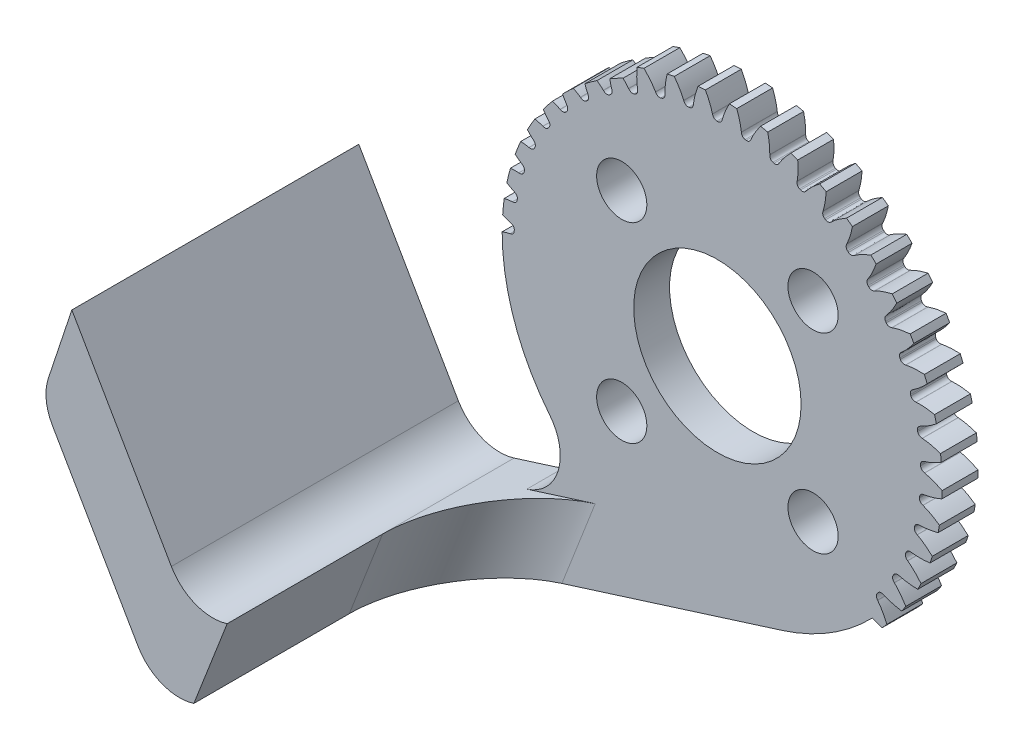
SolidWorks part; units mm, degrees
note: The reader was unsure of these and kept them because the rebuilt part matched: shared geometry of "Sketch1<12>".
ref_plane "Front Plane" through (0, 0, 0) normal (0, 0, 1) x (1, 0, 0)
ref_plane "Top Plane" through (0, 0, 0) normal (0, 1, 0) x (1, 0, 0)
ref_plane "Right Plane" through (0, 0, 0) normal (1, 0, 0) x (0, 0, -1)
sketch "Sketch1" plane through (0, 0, 0) normal (0, 0, 1) x (-1, 0, 0)
  line L0 (-997.4582, 1.777) -> (0.6857, 1.777) construction
  line L3 (27.2085, 36.8505) -> (35.5323, 22.4334)
  line L11 (35.5323, 22.4334) -> (37.4944, 28.3526)
  line L14 (25.33, 45.8357) -> (-2.8709, 36.9439)
  line L15 (22.5416, 38.6653) -> (18.4787, 37.3843)
  line L17 (29.9969, 44.0208) -> (37.1617, 31.6112)
  line L18 (22.5416, 38.6653) -> (25.33, 45.8357)
  line L20 (-14.6013, 17.1719) -> (-14.584, 17.1703)
  line L21 (10.5418, 11.777) -> (-5.4582, 11.777) construction
  line L22 (10.5418, 11.777) -> (10.5418, 27.777) construction
  line L23 (10.5418, 27.777) -> (-5.4582, 27.777) construction
  line L24 (-5.4582, 11.777) -> (-5.4582, 27.777) construction
  line L25 (2.5418, 27.777) -> (2.5418, 11.777) construction
  line L26 (10.5418, 19.777) -> (-5.4582, 19.777) construction
  line L27 (-14.4428, 16.3692) -> (-14.4584, 16.3618)
  line L28 (-14.0719, 14.8114) -> (-14.0546, 14.8122)
  line L29 (-13.8032, 14.0386) -> (-13.8177, 14.0291)
  line L30 (-13.2191, 12.5475) -> (-13.2021, 12.5507)
  line L31 (-12.8455, 11.8196) -> (-12.8585, 11.8082)
  line L32 (-12.0596, 10.4244) -> (-12.0432, 10.4299)
  line L33 (-11.5883, 9.7556) -> (-11.5996, 9.7425)
  line L34 (-10.6158, 8.4833) -> (-10.6003, 8.491)
  line L35 (-10.0561, 7.8866) -> (-10.0654, 7.872)
  line L36 (-8.916, 6.762) -> (-8.9017, 6.7718)
  line L37 (-8.2786, 6.249) -> (-8.2859, 6.2333)
  line L38 (-6.9931, 5.2941) -> (-6.9804, 5.3058)
  line L39 (-6.2906, 4.8747) -> (-6.2956, 4.8582)
  line L40 (-4.8847, 4.108) -> (-4.8737, 4.1214)
  line L41 (-4.1307, 3.7905) -> (-4.1333, 3.7734)
  line L42 (-2.6317, 3.2269) -> (-2.6227, 3.2417)
  line L43 (-1.8408, 3.0175) -> (-1.841, 3.0002)
  line L44 (-0.278, 2.668) -> (-0.2712, 2.6838)
  line L45 (0.5343, 2.5706) -> (0.5365, 2.5535)
  line L46 (2.1305, 2.442) -> (2.1351, 2.4587)
  line L47 (2.9485, 2.4587) -> (2.9531, 2.442)
  line L48 (4.5471, 2.5535) -> (4.5493, 2.5706)
  line L49 (5.3548, 2.6838) -> (5.3617, 2.668)
  line L50 (6.9246, 3.0002) -> (6.9244, 3.0175)
  line L51 (7.7063, 3.2417) -> (7.7153, 3.2269)
  line L52 (9.2169, 3.7734) -> (9.2143, 3.7905)
  line L53 (9.9573, 4.1214) -> (9.9683, 4.108)
  line L54 (11.3792, 4.8582) -> (11.3742, 4.8747)
  line L55 (12.064, 5.3058) -> (12.0767, 5.2941)
  line L56 (13.3695, 6.2333) -> (13.3623, 6.249)
  line L57 (13.9854, 6.7718) -> (13.9996, 6.762)
  line L58 (15.149, 7.872) -> (15.1397, 7.8866)
  line L59 (15.684, 8.491) -> (15.6994, 8.4833)
  line L60 (16.6832, 9.7425) -> (16.6719, 9.7556)
  line L61 (17.1268, 10.4299) -> (17.1432, 10.4244)
  line L62 (17.9421, 11.8082) -> (17.9291, 11.8196)
  line L63 (18.2857, 12.5507) -> (18.3027, 12.5475)
  line L64 (18.9013, 14.0291) -> (18.8868, 14.0386)
  line L65 (19.1382, 14.8122) -> (19.1555, 14.8114)
  line L66 (19.542, 16.3618) -> (19.5264, 16.3692)
  line L67 (19.6676, 17.1703) -> (19.6849, 17.1719)
  line L68 (19.8519, 18.761) -> (19.8354, 18.7662)
  line L69 (19.8638, 19.5791) -> (19.8806, 19.5831)
  line L104 (-10.8652, 30.7736) -> (-10.8548, 30.7597)
  line L105 (-11.3556, 30.1188) -> (-11.3716, 30.1254)
  line L106 (-12.2651, 28.8007) -> (-12.253, 28.7884)
  line L107 (-12.6596, 28.084) -> (-12.6764, 28.0884)
  line L108 (-13.3769, 26.6522) -> (-13.3631, 26.6417)
  line L109 (-13.6678, 25.8875) -> (-13.685, 25.8895)
  line L110 (-14.1788, 24.3698) -> (-14.1637, 24.3613)
  line L111 (-14.3605, 23.5721) -> (-14.3778, 23.5717)
  line L112 (-14.6552, 21.9981) -> (-14.6391, 21.9918)
  line L113 (-14.7242, 21.1828) -> (-14.7412, 21.18)
  line L114 (-14.797, 19.5831) -> (-14.7802, 19.5791)
  line L115 (-14.7518, 18.7662) -> (-14.7683, 18.761)
  arc A0 (-2.8709, 36.9439) -> (-10.4063, 32.2809) centre (2.5418, 19.777) ccw
  circle A2 centre (2.5418, 19.777) radius 7
  circle A4 centre (-5.4582, 27.777) radius 2.1
  circle A5 centre (10.5418, 27.777) radius 2.1
  circle A6 centre (10.5418, 11.777) radius 2.1
  circle A7 centre (-5.4582, 11.777) radius 2.1
  arc A12 (29.9969, 44.0208) -> (25.33, 45.8357) centre (26.5328, 42.0208) ccw
  arc A13 (37.4944, 28.3526) -> (37.1617, 31.6112) centre (33.6976, 29.6112) ccw
  arc A18 (18.4787, 37.3843) -> (16.5652, 31.0617) centre (19.6815, 33.5694) ccw
  arc A19 (27.2085, 36.8505) -> (22.5416, 38.6653) centre (23.7444, 34.8505) ccw
  arc A20 (-16.1848, 18.118) -> (-16.1206, 17.5063) centre (2.5418, 19.777) ccw
  arc A21 (-14.2083, 16.8729) -> (-14.1914, 16.7771) centre (2.5418, 19.777) ccw
  arc A22 (-15.7717, 15.5279) -> (-15.6229, 14.9311) centre (2.5418, 19.777) ccw
  arc A23 (-13.6411, 14.57) -> (-13.6111, 14.4775) centre (2.5418, 19.777) ccw
  arc A24 (-15.0021, 13.0205) -> (-14.7717, 12.4503) centre (2.5418, 19.777) ccw
  arc A25 (-12.7589, 12.3685) -> (-12.7163, 12.281) centre (2.5418, 19.777) ccw
  arc A26 (-13.891, 10.6446) -> (-13.5835, 10.112) centre (2.5418, 19.777) ccw
  arc A27 (-11.579, 10.3111) -> (-11.5246, 10.2305) centre (2.5418, 19.777) ccw
  arc A28 (-12.4601, 8.4465) -> (-12.0815, 7.9618) centre (2.5418, 19.777) ccw
  arc A29 (-10.1241, 8.438) -> (-10.0591, 8.3657) centre (2.5418, 19.777) ccw
  arc A30 (-10.7372, 6.4689) -> (-10.2948, 6.0416) centre (2.5418, 19.777) ccw
  arc A31 (-8.4228, 6.7856) -> (-8.3483, 6.7231) centre (2.5418, 19.777) ccw
  arc A32 (-8.7558, 4.7503) -> (-8.2583, 4.3888) centre (2.5418, 19.777) ccw
  arc A33 (-6.508, 5.386) -> (-6.4255, 5.3345) centre (2.5418, 19.777) ccw
  arc A34 (-6.5546, 3.3242) -> (-6.0116, 3.0355) centre (2.5418, 19.777) ccw
  arc A35 (-4.4171, 4.2666) -> (-4.3283, 4.227) centre (2.5418, 19.777) ccw
  arc A36 (-4.1763, 2.2183) -> (-3.5984, 2.008) centre (2.5418, 19.777) ccw
  arc A37 (-2.1907, 3.4491) -> (-2.0973, 3.4222) centre (2.5418, 19.777) ccw
  arc A38 (-1.6672, 1.4542) -> (-1.0656, 1.3264) centre (2.5418, 19.777) ccw
  arc A39 (0.1277, 2.9493) -> (0.224, 2.9358) centre (2.5418, 19.777) ccw
  arc A40 (0.9238, 1.0468) -> (1.5373, 1.0039) centre (2.5418, 19.777) ccw
  arc A41 (2.4932, 2.7771) -> (2.5904, 2.7771) centre (2.5418, 19.777) ccw
  arc A42 (3.5463, 1.0039) -> (4.1598, 1.0468) centre (2.5418, 19.777) ccw
  arc A43 (4.8596, 2.9358) -> (4.9559, 2.9493) centre (2.5418, 19.777) ccw
  arc A44 (6.1492, 1.3264) -> (6.7508, 1.4542) centre (2.5418, 19.777) ccw
  arc A45 (7.1809, 3.4222) -> (7.2744, 3.4491) centre (2.5418, 19.777) ccw
  arc A46 (8.682, 2.008) -> (9.2599, 2.2183) centre (2.5418, 19.777) ccw
  arc A47 (9.4119, 4.227) -> (9.5007, 4.2666) centre (2.5418, 19.777) ccw
  arc A49 (11.5092, 5.3345) -> (11.5916, 5.386) centre (2.5418, 19.777) ccw
  arc A51 (13.4319, 6.7231) -> (13.5064, 6.7856) centre (2.5418, 19.777) ccw
  arc A53 (15.1427, 8.3657) -> (15.2078, 8.438) centre (2.5418, 19.777) ccw
  arc A55 (16.6082, 10.2305) -> (16.6626, 10.3111) centre (2.5418, 19.777) ccw
  arc A57 (17.7999, 12.281) -> (17.8426, 12.3685) centre (2.5418, 19.777) ccw
  arc A59 (18.6947, 14.4775) -> (18.7247, 14.57) centre (2.5418, 19.777) ccw
  arc A61 (19.275, 16.7771) -> (19.2919, 16.8729) centre (2.5418, 19.777) ccw
  arc A63 (19.5297, 19.1351) -> (19.5331, 19.2323) centre (2.5418, 19.777) ccw
  arc A98 (-11.2217, 32.5835) -> (-11.6332, 32.1265) centre (2.5418, 19.777) ccw
  arc A99 (-10.8244, 30.2816) -> (-10.8843, 30.2049) centre (2.5418, 19.777) ccw
  arc A100 (-12.8701, 30.5434) -> (-13.214, 30.0335) centre (2.5418, 19.777) ccw
  arc A101 (-12.1563, 28.3191) -> (-12.2049, 28.2349) centre (2.5418, 19.777) ccw
  arc A102 (-14.2185, 28.2937) -> (-14.4881, 27.7409) centre (2.5418, 19.777) ccw
  arc A103 (-13.202, 26.1904) -> (-13.2385, 26.1002) centre (2.5418, 19.777) ccw
  arc A104 (-15.2406, 25.8782) -> (-15.4307, 25.2933) centre (2.5418, 19.777) ccw
  arc A105 (-13.9414, 23.9369) -> (-13.9649, 23.8425) centre (2.5418, 19.777) ccw
  arc A106 (-15.9167, 23.344) -> (-16.0235, 22.7384) centre (2.5418, 19.777) ccw
  arc A107 (-14.3599, 21.6024) -> (-14.3701, 21.5056) centre (2.5418, 19.777) ccw
  arc A108 (-16.2335, 20.7404) -> (-16.255, 20.1257) centre (2.5418, 19.777) ccw
  arc A109 (-14.4495, 19.2323) -> (-14.4461, 19.1351) centre (2.5418, 19.777) ccw
  arc A110 (10.4325, 3.5987) -> (11.5418, 4.1886) centre (2.5418, 19.777) ccw
  arc A113 (12.6073, 4.8544) -> (13.6237, 5.5928) centre (2.5418, 19.777) ccw
  arc A114 (14.5862, 6.4004) -> (15.4899, 7.2732) centre (2.5418, 19.777) ccw
  arc A115 (20.5418, 19.777) -> (16.5652, 31.0617) centre (2.5418, 19.777) ccw
  arc A116 (20.3666, 17.2719) -> (20.498, 18.5214) centre (2.5418, 19.777) ccw
  arc A117 (19.8445, 14.8156) -> (20.1485, 16.0346) centre (2.5418, 19.777) ccw
  arc A118 (18.9856, 12.4558) -> (19.4563, 13.6207) centre (2.5418, 19.777) ccw
  arc A119 (17.8067, 10.2385) -> (18.4349, 11.3265) centre (2.5418, 19.777) ccw
  arc A120 (16.3306, 8.2069) -> (17.1041, 9.1969) centre (2.5418, 19.777) ccw
  spline S0 degree 3 poles (-14.7683, 18.761) (-14.8625, 18.7338) (-15.0114, 18.6848) (-15.2184, 18.6056) (-15.3979, 18.53) (-15.5921, 18.4404) (-15.8001, 18.3357) (-15.9995, 18.227) (-16.1287, 18.1517) (-16.1848, 18.118) knots 0 0 0 0 0.131774 0.210453 0.29766 0.393396 0.49766 0.610453 0.698458 0.698458 0.698458 0.698458 weights 1 1 1 1 1 1 1 1 1 1
  spline S1 degree 3 poles (-16.1206, 17.5063) (-16.0586, 17.4851) (-15.9166, 17.4382) (-15.699, 17.3733) (-15.4737, 17.3143) (-15.2652, 17.267) (-15.0739, 17.2303) (-14.8549, 17.1959) (-14.6991, 17.1789) (-14.6013, 17.1719) knots 0.301542 0.301542 0.301542 0.301542 0.389547 0.50234 0.606604 0.70234 0.789547 0.868226 1 1 1 1 weights 1 1 1 1 1 1 1 1 1 1
  spline S2 degree 3 poles (-14.584, 17.1703) (-14.5667, 17.1689) (-14.5374, 17.165) (-14.496, 17.1567) (-14.4585, 17.1463) (-14.4182, 17.1314) (-14.3741, 17.1095) (-14.326, 17.0767) (-14.254, 17.0064) (-14.218, 16.9305) (-14.2083, 16.8729) knots 0 0 0 0 0.101113 0.170973 0.245147 0.32664 0.419682 0.529844 0.663118 1 1 1 1 weights 1 1 1 1 1 1 1 1 1 1 1
  spline S3 degree 3 poles (-14.1914, 16.7771) (-14.1809, 16.7197) (-14.1887, 16.6361) (-14.2323, 16.5453) (-14.2663, 16.4981) (-14.3002, 16.4624) (-14.333, 16.4347) (-14.3647, 16.4121) (-14.4008, 16.3901) (-14.4269, 16.3764) (-14.4428, 16.3692) knots 0 0 0 0 0.336882 0.470156 0.580318 0.67336 0.754853 0.829027 0.898887 1 1 1 1 weights 1 1 1 1 1 1 1 1 1 1 1
  spline S4 degree 3 poles (-14.4584, 16.3618) (-14.548, 16.3218) (-14.6886, 16.2525) (-14.8825, 16.1453) (-15.0498, 16.0454) (-15.2296, 15.9296) (-15.421, 15.7971) (-15.6034, 15.6616) (-15.7207, 15.5691) (-15.7717, 15.5279) knots 0 0 0 0 0.131774 0.210453 0.29766 0.393396 0.49766 0.610453 0.698458 0.698458 0.698458 0.698458 weights 1 1 1 1 1 1 1 1 1 1
  spline S5 degree 3 poles (-15.6229, 14.9311) (-15.5586, 14.9187) (-15.4115, 14.8921) (-15.1869, 14.8581) (-14.9556, 14.8309) (-14.7425, 14.8132) (-14.548, 14.8035) (-14.3264, 14.7998) (-14.1697, 14.8047) (-14.0719, 14.8114) knots 0.301542 0.301542 0.301542 0.301542 0.389547 0.50234 0.606604 0.70234 0.789547 0.868226 1 1 1 1 weights 1 1 1 1 1 1 1 1 1 1
  spline S6 degree 3 poles (-14.0546, 14.8122) (-14.0372, 14.8133) (-14.0077, 14.8135) (-13.9655, 14.811) (-13.9269, 14.806) (-13.8849, 14.7968) (-13.8383, 14.7812) (-13.7861, 14.7555) (-13.705, 14.6958) (-13.6588, 14.6257) (-13.6411, 14.57) knots 0 0 0 0 0.101113 0.170973 0.245147 0.32664 0.419682 0.529844 0.663118 1 1 1 1 weights 1 1 1 1 1 1 1 1 1 1 1
  spline S7 degree 3 poles (-13.6111, 14.4775) (-13.5926, 14.4221) (-13.5888, 14.3382) (-13.6193, 14.2423) (-13.6464, 14.1907) (-13.675, 14.1507) (-13.7036, 14.1187) (-13.7318, 14.0919) (-13.7645, 14.0651) (-13.7885, 14.0479) (-13.8032, 14.0386) knots 0 0 0 0 0.336882 0.470156 0.580318 0.67336 0.754853 0.829027 0.898887 1 1 1 1 weights 1 1 1 1 1 1 1 1 1 1 1
  spline S8 degree 3 poles (-13.8177, 14.0291) (-13.9008, 13.9769) (-14.0304, 13.8888) (-14.2075, 13.7556) (-14.3592, 13.6334) (-14.5212, 13.4938) (-14.6923, 13.3359) (-14.854, 13.1763) (-14.9574, 13.0683) (-15.0021, 13.0205) knots 0 0 0 0 0.131774 0.210453 0.29766 0.393396 0.49766 0.610453 0.698458 0.698458 0.698458 0.698458 weights 1 1 1 1 1 1 1 1 1 1
  spline S9 degree 3 poles (-14.7717, 12.4503) (-14.7063, 12.4469) (-14.5569, 12.441) (-14.3298, 12.4386) (-14.097, 12.4439) (-13.8835, 12.456) (-13.6895, 12.4734) (-13.4696, 12.5007) (-13.3151, 12.5273) (-13.2191, 12.5475) knots 0.301542 0.301542 0.301542 0.301542 0.389547 0.50234 0.606604 0.70234 0.789547 0.868226 1 1 1 1 weights 1 1 1 1 1 1 1 1 1 1
  spline S10 degree 3 poles (-13.2021, 12.5507) (-13.185, 12.5543) (-13.1558, 12.5585) (-13.1137, 12.562) (-13.0748, 12.5623) (-13.032, 12.5591) (-12.9836, 12.5502) (-12.9283, 12.5319) (-12.8397, 12.4841) (-12.7842, 12.4211) (-12.7589, 12.3685) knots 0 0 0 0 0.101113 0.170973 0.245147 0.32664 0.419682 0.529844 0.663118 1 1 1 1 weights 1 1 1 1 1 1 1 1 1 1 1
  spline S11 degree 3 poles (-12.7163, 12.281) (-12.6904, 12.2288) (-12.6749, 12.1462) (-12.6918, 12.0469) (-12.7114, 11.9921) (-12.7342, 11.9485) (-12.758, 11.9128) (-12.7822, 11.8824) (-12.8109, 11.8513) (-12.8322, 11.8309) (-12.8455, 11.8196) knots 0 0 0 0 0.336882 0.470156 0.580318 0.67336 0.754853 0.829027 0.898887 1 1 1 1 weights 1 1 1 1 1 1 1 1 1 1 1
  spline S12 degree 3 poles (-12.8585, 11.8082) (-12.9335, 11.745) (-13.0496, 11.6397) (-13.2065, 11.4831) (-13.3397, 11.341) (-13.4806, 11.1802) (-13.6282, 11) (-13.7661, 10.8196) (-13.8534, 10.6982) (-13.891, 10.6446) knots 0 0 0 0 0.131774 0.210453 0.29766 0.393396 0.49766 0.610453 0.698458 0.698458 0.698458 0.698458 weights 1 1 1 1 1 1 1 1 1 1
  spline S13 degree 3 poles (-13.5835, 10.112) (-13.5183, 10.1178) (-13.3695, 10.1327) (-13.1443, 10.1619) (-12.9145, 10.1996) (-12.7047, 10.2412) (-12.5151, 10.2855) (-12.3011, 10.3431) (-12.1518, 10.391) (-12.0596, 10.4244) knots 0.301542 0.301542 0.301542 0.301542 0.389547 0.50234 0.606604 0.70234 0.789547 0.868226 1 1 1 1 weights 1 1 1 1 1 1 1 1 1 1
  spline S14 degree 3 poles (-12.0432, 10.4299) (-12.0267, 10.4358) (-11.9984, 10.4441) (-11.9572, 10.4533) (-11.9187, 10.4591) (-11.8759, 10.4619) (-11.8267, 10.4598) (-11.7694, 10.4494) (-11.675, 10.4144) (-11.6113, 10.3597) (-11.579, 10.3111) knots 0 0 0 0 0.101113 0.170973 0.245147 0.32664 0.419682 0.529844 0.663118 1 1 1 1 weights 1 1 1 1 1 1 1 1 1 1 1
  spline S15 degree 3 poles (-11.5246, 10.2305) (-11.4916, 10.1823) (-11.4648, 10.1027) (-11.4677, 10.0021) (-11.4795, 9.9451) (-11.496, 9.8987) (-11.5146, 9.86) (-11.5344, 9.8265) (-11.5584, 9.7917) (-11.5767, 9.7686) (-11.5883, 9.7556) knots 0 0 0 0 0.336882 0.470156 0.580318 0.67336 0.754853 0.829027 0.898887 1 1 1 1 weights 1 1 1 1 1 1 1 1 1 1 1
  spline S16 degree 3 poles (-11.5996, 9.7425) (-11.6651, 9.6694) (-11.7654, 9.549) (-11.8989, 9.3721) (-12.0111, 9.2128) (-12.1283, 9.034) (-12.2493, 8.835) (-12.3607, 8.6371) (-12.4303, 8.5048) (-12.4601, 8.4465) knots 0 0 0 0 0.131774 0.210453 0.29766 0.393396 0.49766 0.610453 0.698458 0.698458 0.698458 0.698458 weights 1 1 1 1 1 1 1 1 1 1
  spline S17 degree 3 poles (-12.0815, 7.9618) (-12.0177, 7.9766) (-11.8725, 8.0121) (-11.6535, 8.0724) (-11.4311, 8.1417) (-11.2292, 8.2121) (-11.0476, 8.2824) (-10.8437, 8.3692) (-10.7025, 8.4374) (-10.6158, 8.4833) knots 0.301542 0.301542 0.301542 0.301542 0.389547 0.50234 0.606604 0.70234 0.789547 0.868226 1 1 1 1 weights 1 1 1 1 1 1 1 1 1 1
  spline S18 degree 3 poles (-10.6003, 8.491) (-10.5849, 8.4991) (-10.558, 8.5113) (-10.5185, 8.5262) (-10.4812, 8.5373) (-10.4391, 8.546) (-10.3902, 8.5508) (-10.332, 8.5485) (-10.2336, 8.5269) (-10.1629, 8.4817) (-10.1241, 8.438) knots 0 0 0 0 0.101113 0.170973 0.245147 0.32664 0.419682 0.529844 0.663118 1 1 1 1 weights 1 1 1 1 1 1 1 1 1 1 1
  spline S19 degree 3 poles (-10.0591, 8.3657) (-10.0197, 8.3226) (-9.9821, 8.2475) (-9.9709, 8.1475) (-9.9747, 8.0894) (-9.9846, 8.0412) (-9.9976, 8.0003) (-10.0125, 7.9643) (-10.0315, 7.9265) (-10.0464, 7.9011) (-10.0561, 7.8866) knots 0 0 0 0 0.336882 0.470156 0.580318 0.67336 0.754853 0.829027 0.898887 1 1 1 1 weights 1 1 1 1 1 1 1 1 1 1 1
  spline S20 degree 3 poles (-10.0654, 7.872) (-10.1201, 7.7906) (-10.2027, 7.6573) (-10.3103, 7.4636) (-10.3992, 7.2903) (-10.4903, 7.0968) (-10.5825, 6.883) (-10.6653, 6.6715) (-10.7158, 6.5308) (-10.7372, 6.4689) knots 0 0 0 0 0.131774 0.210453 0.29766 0.393396 0.49766 0.610453 0.698458 0.698458 0.698458 0.698458 weights 1 1 1 1 1 1 1 1 1 1
  spline S21 degree 3 poles (-10.2948, 6.0416) (-10.2337, 6.0652) (-10.0948, 6.1206) (-9.8864, 6.2107) (-9.6758, 6.3103) (-9.4857, 6.4081) (-9.3156, 6.503) (-9.1257, 6.6174) (-8.9954, 6.7045) (-8.916, 6.762) knots 0.301542 0.301542 0.301542 0.301542 0.389547 0.50234 0.606604 0.70234 0.789547 0.868226 1 1 1 1 weights 1 1 1 1 1 1 1 1 1 1
  spline S22 degree 3 poles (-8.9017, 6.7718) (-8.8876, 6.782) (-8.8627, 6.7978) (-8.8256, 6.8181) (-8.7902, 6.8342) (-8.7497, 6.8487) (-8.7019, 6.8602) (-8.644, 6.866) (-8.5436, 6.8584) (-8.4672, 6.8234) (-8.4228, 6.7856) knots 0 0 0 0 0.101113 0.170973 0.245147 0.32664 0.419682 0.529844 0.663118 1 1 1 1 weights 1 1 1 1 1 1 1 1 1 1 1
  spline S23 degree 3 poles (-8.3483, 6.7231) (-8.3033, 6.6859) (-8.2556, 6.6167) (-8.2306, 6.5192) (-8.2263, 6.4611) (-8.2294, 6.412) (-8.2366, 6.3697) (-8.2464, 6.3321) (-8.2599, 6.292) (-8.2711, 6.2647) (-8.2786, 6.249) knots 0 0 0 0 0.336882 0.470156 0.580318 0.67336 0.754853 0.829027 0.898887 1 1 1 1 weights 1 1 1 1 1 1 1 1 1 1 1
  spline S24 degree 3 poles (-8.2859, 6.2333) (-8.3287, 6.145) (-8.3919, 6.0016) (-8.4716, 5.7948) (-8.5354, 5.6108) (-8.5988, 5.4065) (-8.6603, 5.1819) (-8.7129, 4.961) (-8.7433, 4.8146) (-8.7558, 4.7503) knots 0 0 0 0 0.131774 0.210453 0.29766 0.393396 0.49766 0.610453 0.698458 0.698458 0.698458 0.698458 weights 1 1 1 1 1 1 1 1 1 1
  spline S25 degree 3 poles (-8.2583, 4.3888) (-8.201, 4.4206) (-8.0712, 4.4948) (-7.8774, 4.6131) (-7.6827, 4.741) (-7.5081, 4.8643) (-7.3528, 4.9819) (-7.1807, 5.1216) (-7.0638, 5.226) (-6.9931, 5.2941) knots 0.301542 0.301542 0.301542 0.301542 0.389547 0.50234 0.606604 0.70234 0.789547 0.868226 1 1 1 1 weights 1 1 1 1 1 1 1 1 1 1
  spline S26 degree 3 poles (-6.9804, 5.3058) (-6.9678, 5.3178) (-6.9453, 5.3369) (-6.9114, 5.3622) (-6.8786, 5.3831) (-6.8406, 5.403) (-6.7948, 5.4211) (-6.7383, 5.4349) (-6.6378, 5.4414) (-6.5573, 5.4173) (-6.508, 5.386) knots 0 0 0 0 0.101113 0.170973 0.245147 0.32664 0.419682 0.529844 0.663118 1 1 1 1 weights 1 1 1 1 1 1 1 1 1 1 1
  spline S27 degree 3 poles (-6.4255, 5.3345) (-6.3758, 5.3039) (-6.3189, 5.2421) (-6.2807, 5.149) (-6.2683, 5.0921) (-6.2645, 5.0431) (-6.2657, 5.0001) (-6.2702, 4.9615) (-6.278, 4.9199) (-6.2853, 4.8914) (-6.2906, 4.8747) knots 0 0 0 0 0.336882 0.470156 0.580318 0.67336 0.754853 0.829027 0.898887 1 1 1 1 weights 1 1 1 1 1 1 1 1 1 1 1
  spline S28 degree 3 poles (-6.2956, 4.8582) (-6.3257, 4.7648) (-6.3683, 4.614) (-6.4184, 4.3981) (-6.4561, 4.207) (-6.4904, 3.9959) (-6.52, 3.7649) (-6.5413, 3.5388) (-6.5511, 3.3896) (-6.5546, 3.3242) knots 0 0 0 0 0.131774 0.210453 0.29766 0.393396 0.49766 0.610453 0.698458 0.698458 0.698458 0.698458 weights 1 1 1 1 1 1 1 1 1 1
  spline S29 degree 3 poles (-6.0116, 3.0355) (-5.9593, 3.075) (-5.8411, 3.1665) (-5.6655, 3.3106) (-5.4906, 3.4643) (-5.3348, 3.6108) (-5.1974, 3.7489) (-5.0465, 3.9111) (-4.9452, 4.0308) (-4.8847, 4.108) knots 0.301542 0.301542 0.301542 0.301542 0.389547 0.50234 0.606604 0.70234 0.789547 0.868226 1 1 1 1 weights 1 1 1 1 1 1 1 1 1 1
  spline S30 degree 3 poles (-4.8737, 4.1214) (-4.8629, 4.1351) (-4.8433, 4.1571) (-4.8132, 4.1868) (-4.7837, 4.2121) (-4.7488, 4.2372) (-4.706, 4.2614) (-4.6519, 4.283) (-4.5533, 4.3033) (-4.4703, 4.2907) (-4.4171, 4.2666) knots 0 0 0 0 0.101113 0.170973 0.245147 0.32664 0.419682 0.529844 0.663118 1 1 1 1 weights 1 1 1 1 1 1 1 1 1 1 1
  spline S31 degree 3 poles (-4.3283, 4.227) (-4.2748, 4.2037) (-4.2098, 4.1504) (-4.159, 4.0635) (-4.1388, 4.0089) (-4.1282, 3.9608) (-4.1235, 3.9182) (-4.1225, 3.8793) (-4.1244, 3.837) (-4.1277, 3.8077) (-4.1307, 3.7905) knots 0 0 0 0 0.336882 0.470156 0.580318 0.67336 0.754853 0.829027 0.898887 1 1 1 1 weights 1 1 1 1 1 1 1 1 1 1 1
  spline S32 degree 3 poles (-4.1333, 3.7734) (-4.1501, 3.6768) (-4.1713, 3.5215) (-4.1909, 3.3007) (-4.2016, 3.1062) (-4.2062, 2.8925) (-4.2034, 2.6596) (-4.193, 2.4327) (-4.1819, 2.2836) (-4.1763, 2.2183) knots 0 0 0 0 0.131774 0.210453 0.29766 0.393396 0.49766 0.610453 0.698458 0.698458 0.698458 0.698458 weights 1 1 1 1 1 1 1 1 1 1
  spline S33 degree 3 poles (-3.5984, 2.008) (-3.5521, 2.0544) (-3.4477, 2.1614) (-3.294, 2.3286) (-3.1421, 2.5052) (-3.0082, 2.6719) (-2.8914, 2.8278) (-2.7645, 3.0094) (-2.6809, 3.142) (-2.6317, 3.2269) knots 0.301542 0.301542 0.301542 0.301542 0.389547 0.50234 0.606604 0.70234 0.789547 0.868226 1 1 1 1 weights 1 1 1 1 1 1 1 1 1 1
  spline S34 degree 3 poles (-2.6227, 3.2417) (-2.6139, 3.2567) (-2.5976, 3.2813) (-2.5719, 3.3149) (-2.5462, 3.3441) (-2.5151, 3.3737) (-2.4761, 3.4037) (-2.4256, 3.4326) (-2.3307, 3.4664) (-2.2468, 3.4655) (-2.1907, 3.4491) knots 0 0 0 0 0.101113 0.170973 0.245147 0.32664 0.419682 0.529844 0.663118 1 1 1 1 weights 1 1 1 1 1 1 1 1 1 1 1
  spline S35 degree 3 poles (-2.0973, 3.4222) (-2.041, 3.4065) (-1.9693, 3.3628) (-1.9069, 3.2839) (-1.8793, 3.2326) (-1.8621, 3.1865) (-1.8515, 3.1449) (-1.8451, 3.1065) (-1.8411, 3.0644) (-1.8403, 3.0349) (-1.8408, 3.0175) knots 0 0 0 0 0.336882 0.470156 0.580318 0.67336 0.754853 0.829027 0.898887 1 1 1 1 weights 1 1 1 1 1 1 1 1 1 1 1
  spline S36 degree 3 poles (-1.841, 3.0002) (-1.8443, 2.9021) (-1.8437, 2.7454) (-1.8323, 2.5241) (-1.8158, 2.33) (-1.7906, 2.1176) (-1.7554, 1.8874) (-1.7136, 1.6642) (-1.6819, 1.5181) (-1.6672, 1.4542) knots 0 0 0 0 0.131774 0.210453 0.29766 0.393396 0.49766 0.610453 0.698458 0.698458 0.698458 0.698458 weights 1 1 1 1 1 1 1 1 1 1
  spline S37 degree 3 poles (-1.0656, 1.3264) (-1.0263, 1.3787) (-0.9378, 1.4993) (-0.8088, 1.6862) (-0.6831, 1.8822) (-0.5737, 2.0659) (-0.4797, 2.2366) (-0.3793, 2.4341) (-0.3149, 2.5771) (-0.278, 2.668) knots 0.301542 0.301542 0.301542 0.301542 0.389547 0.50234 0.606604 0.70234 0.789547 0.868226 1 1 1 1 weights 1 1 1 1 1 1 1 1 1 1
  spline S38 degree 3 poles (-0.2712, 2.6838) (-0.2646, 2.7) (-0.2518, 2.7266) (-0.2311, 2.7634) (-0.2096, 2.7959) (-0.183, 2.8296) (-0.1486, 2.8647) (-0.1025, 2.9003) (-0.0133, 2.9471) (0.07, 2.9578) (0.1277, 2.9493) knots 0 0 0 0 0.101113 0.170973 0.245147 0.32664 0.419682 0.529844 0.663118 1 1 1 1 weights 1 1 1 1 1 1 1 1 1 1 1
  spline S39 degree 3 poles (0.224, 2.9358) (0.2819, 2.9281) (0.359, 2.8947) (0.4318, 2.8252) (0.4663, 2.7783) (0.4897, 2.735) (0.506, 2.6953) (0.5177, 2.6582) (0.5275, 2.6171) (0.5324, 2.588) (0.5343, 2.5706) knots 0 0 0 0 0.336882 0.470156 0.580318 0.67336 0.754853 0.829027 0.898887 1 1 1 1 weights 1 1 1 1 1 1 1 1 1 1 1
  spline S40 degree 3 poles (0.5365, 2.5535) (0.5469, 2.4559) (0.5694, 2.3008) (0.6114, 2.0832) (0.6547, 1.8933) (0.7093, 1.6865) (0.7761, 1.4635) (0.8486, 1.2482) (0.9004, 1.108) (0.9238, 1.0468) knots 0 0 0 0 0.131774 0.210453 0.29766 0.393396 0.49766 0.610453 0.698458 0.698458 0.698458 0.698458 weights 1 1 1 1 1 1 1 1 1 1
  spline S41 degree 3 poles (1.5373, 1.0039) (1.569, 1.0612) (1.6398, 1.1929) (1.7415, 1.396) (1.8388, 1.6076) (1.9216, 1.8047) (1.9909, 1.9868) (2.0628, 2.1964) (2.1066, 2.3469) (2.1305, 2.442) knots 0.301542 0.301542 0.301542 0.301542 0.389547 0.50234 0.606604 0.70234 0.789547 0.868226 1 1 1 1 weights 1 1 1 1 1 1 1 1 1 1
  spline S42 degree 3 poles (2.1351, 2.4587) (2.1394, 2.4756) (2.1483, 2.5037) (2.1638, 2.5431) (2.1805, 2.5782) (2.2021, 2.6153) (2.2314, 2.6549) (2.272, 2.6965) (2.3538, 2.7552) (2.4348, 2.7775) (2.4932, 2.7771) knots 0 0 0 0 0.101113 0.170973 0.245147 0.32664 0.419682 0.529844 0.663118 1 1 1 1 weights 1 1 1 1 1 1 1 1 1 1 1
  spline S43 degree 3 poles (2.5904, 2.7771) (2.6488, 2.7775) (2.7298, 2.7552) (2.8116, 2.6965) (2.8523, 2.6549) (2.8815, 2.6153) (2.9031, 2.5782) (2.9199, 2.5431) (2.9353, 2.5037) (2.9442, 2.4756) (2.9485, 2.4587) knots 0 0 0 0 0.336882 0.470156 0.580318 0.67336 0.754853 0.829027 0.898887 1 1 1 1 weights 1 1 1 1 1 1 1 1 1 1 1
  spline S44 degree 3 poles (2.9531, 2.442) (2.977, 2.3469) (3.0208, 2.1964) (3.0927, 1.9868) (3.162, 1.8047) (3.2448, 1.6076) (3.3421, 1.396) (3.4438, 1.1929) (3.5146, 1.0612) (3.5463, 1.0039) knots 0 0 0 0 0.131774 0.210453 0.29766 0.393396 0.49766 0.610453 0.698458 0.698458 0.698458 0.698458 weights 1 1 1 1 1 1 1 1 1 1
  spline S45 degree 3 poles (4.1598, 1.0468) (4.1832, 1.108) (4.235, 1.2482) (4.3075, 1.4635) (4.3744, 1.6865) (4.4289, 1.8933) (4.4722, 2.0832) (4.5142, 2.3008) (4.5367, 2.4559) (4.5471, 2.5535) knots 0.301542 0.301542 0.301542 0.301542 0.389547 0.50234 0.606604 0.70234 0.789547 0.868226 1 1 1 1 weights 1 1 1 1 1 1 1 1 1 1
  spline S46 degree 3 poles (4.5493, 2.5706) (4.5512, 2.588) (4.5562, 2.6171) (4.5659, 2.6582) (4.5776, 2.6953) (4.5939, 2.735) (4.6173, 2.7783) (4.6518, 2.8252) (4.7246, 2.8947) (4.8017, 2.9281) (4.8596, 2.9358) knots 0 0 0 0 0.101113 0.170973 0.245147 0.32664 0.419682 0.529844 0.663118 1 1 1 1 weights 1 1 1 1 1 1 1 1 1 1 1
  spline S47 degree 3 poles (4.9559, 2.9493) (5.0136, 2.9578) (5.0969, 2.9471) (5.1861, 2.9003) (5.2322, 2.8647) (5.2666, 2.8296) (5.2932, 2.7959) (5.3147, 2.7634) (5.3354, 2.7266) (5.3482, 2.7) (5.3548, 2.6838) knots 0 0 0 0 0.336882 0.470156 0.580318 0.67336 0.754853 0.829027 0.898887 1 1 1 1 weights 1 1 1 1 1 1 1 1 1 1 1
  spline S48 degree 3 poles (5.3617, 2.668) (5.3986, 2.5771) (5.4629, 2.4341) (5.5633, 2.2366) (5.6573, 2.0659) (5.7667, 1.8822) (5.8924, 1.6862) (6.0215, 1.4993) (6.1099, 1.3787) (6.1492, 1.3264) knots 0 0 0 0 0.131774 0.210453 0.29766 0.393396 0.49766 0.610453 0.698458 0.698458 0.698458 0.698458 weights 1 1 1 1 1 1 1 1 1 1
  spline S49 degree 3 poles (6.7508, 1.4542) (6.7655, 1.5181) (6.7972, 1.6642) (6.839, 1.8874) (6.8742, 2.1176) (6.8994, 2.33) (6.9159, 2.5241) (6.9273, 2.7454) (6.9279, 2.9021) (6.9246, 3.0002) knots 0.301542 0.301542 0.301542 0.301542 0.389547 0.50234 0.606604 0.70234 0.789547 0.868226 1 1 1 1 weights 1 1 1 1 1 1 1 1 1 1
  spline S50 degree 3 poles (6.9244, 3.0175) (6.9239, 3.0349) (6.9248, 3.0644) (6.9287, 3.1065) (6.9351, 3.1449) (6.9457, 3.1865) (6.9629, 3.2326) (6.9905, 3.2839) (7.0529, 3.3628) (7.1247, 3.4065) (7.1809, 3.4222) knots 0 0 0 0 0.101113 0.170973 0.245147 0.32664 0.419682 0.529844 0.663118 1 1 1 1 weights 1 1 1 1 1 1 1 1 1 1 1
  spline S51 degree 3 poles (7.2744, 3.4491) (7.3304, 3.4655) (7.4144, 3.4664) (7.5092, 3.4326) (7.5597, 3.4037) (7.5987, 3.3737) (7.6298, 3.3441) (7.6555, 3.3149) (7.6812, 3.2813) (7.6975, 3.2567) (7.7063, 3.2417) knots 0 0 0 0 0.336882 0.470156 0.580318 0.67336 0.754853 0.829027 0.898887 1 1 1 1 weights 1 1 1 1 1 1 1 1 1 1 1
  spline S52 degree 3 poles (7.7153, 3.2269) (7.7645, 3.142) (7.8481, 3.0094) (7.975, 2.8278) (8.0919, 2.6719) (8.2258, 2.5052) (8.3776, 2.3286) (8.5314, 2.1614) (8.6357, 2.0544) (8.682, 2.008) knots 0 0 0 0 0.131774 0.210453 0.29766 0.393396 0.49766 0.610453 0.698458 0.698458 0.698458 0.698458 weights 1 1 1 1 1 1 1 1 1 1
  spline S53 degree 3 poles (9.2599, 2.2183) (9.2655, 2.2836) (9.2766, 2.4327) (9.287, 2.6596) (9.2898, 2.8925) (9.2852, 3.1062) (9.2745, 3.3007) (9.2549, 3.5215) (9.2337, 3.6768) (9.2169, 3.7734) knots 0.301542 0.301542 0.301542 0.301542 0.389547 0.50234 0.606604 0.70234 0.789547 0.868226 1 1 1 1 weights 1 1 1 1 1 1 1 1 1 1
  spline S54 degree 3 poles (9.2143, 3.7905) (9.2113, 3.8077) (9.2081, 3.837) (9.2061, 3.8793) (9.2071, 3.9182) (9.2118, 3.9608) (9.2224, 4.0089) (9.2426, 4.0635) (9.2935, 4.1504) (9.3584, 4.2037) (9.4119, 4.227) knots 0 0 0 0 0.101113 0.170973 0.245147 0.32664 0.419682 0.529844 0.663118 1 1 1 1 weights 1 1 1 1 1 1 1 1 1 1 1
  spline S55 degree 3 poles (9.5007, 4.2666) (9.5539, 4.2907) (9.6369, 4.3033) (9.7355, 4.283) (9.7896, 4.2614) (9.8324, 4.2372) (9.8673, 4.2121) (9.8968, 4.1868) (9.9269, 4.1571) (9.9465, 4.1351) (9.9573, 4.1214) knots 0 0 0 0 0.336882 0.470156 0.580318 0.67336 0.754853 0.829027 0.898887 1 1 1 1 weights 1 1 1 1 1 1 1 1 1 1 1
  spline S56 degree 3 poles (9.9683, 4.108) (10.0288, 4.0308) (10.1301, 3.9111) (10.2867, 3.7428) (10.3798, 3.6496) (10.4325, 3.5987) knots 0 0 0 0 0.131774 0.210453 0.308781 0.308781 0.308781 0.308781 weights 1 1 1 1 1 1
  spline S57 degree 3 poles (11.5418, 4.1886) (11.5291, 4.2607) (11.5039, 4.39) (11.4519, 4.614) (11.4093, 4.7648) (11.3792, 4.8582) knots 0.691219 0.691219 0.691219 0.691219 0.789547 0.868226 1 1 1 1 weights 1 1 1 1 1 1
  spline S58 degree 3 poles (11.3742, 4.8747) (11.3689, 4.8914) (11.3616, 4.9199) (11.3538, 4.9615) (11.3494, 5.0001) (11.3481, 5.0431) (11.3519, 5.0921) (11.3643, 5.149) (11.4026, 5.2421) (11.4594, 5.3039) (11.5092, 5.3345) knots 0 0 0 0 0.101113 0.170973 0.245147 0.32664 0.419682 0.529844 0.663118 1 1 1 1 weights 1 1 1 1 1 1 1 1 1 1 1
  spline S59 degree 3 poles (11.5916, 5.386) (11.6409, 5.4173) (11.7214, 5.4414) (11.8219, 5.4349) (11.8784, 5.4211) (11.9242, 5.403) (11.9622, 5.3831) (11.995, 5.3622) (12.0289, 5.3369) (12.0514, 5.3178) (12.064, 5.3058) knots 0 0 0 0 0.336882 0.470156 0.580318 0.67336 0.754853 0.829027 0.898887 1 1 1 1 weights 1 1 1 1 1 1 1 1 1 1 1
  spline S60 degree 3 poles (12.0767, 5.2941) (12.1474, 5.226) (12.2643, 5.1216) (12.4428, 4.9767) (12.5481, 4.8974) (12.6073, 4.8544) knots 0 0 0 0 0.131774 0.210453 0.308781 0.308781 0.308781 0.308781 weights 1 1 1 1 1 1
  spline S61 degree 3 poles (13.6237, 5.5928) (13.6011, 5.6625) (13.5581, 5.7871) (13.4755, 6.0016) (13.4123, 6.145) (13.3695, 6.2333) knots 0.691219 0.691219 0.691219 0.691219 0.789547 0.868226 1 1 1 1 weights 1 1 1 1 1 1
  spline S62 degree 3 poles (13.3623, 6.249) (13.3547, 6.2647) (13.3435, 6.292) (13.33, 6.3321) (13.3202, 6.3697) (13.313, 6.412) (13.3099, 6.4611) (13.3143, 6.5192) (13.3392, 6.6167) (13.3869, 6.6859) (13.4319, 6.7231) knots 0 0 0 0 0.101113 0.170973 0.245147 0.32664 0.419682 0.529844 0.663118 1 1 1 1 weights 1 1 1 1 1 1 1 1 1 1 1
  spline S63 degree 3 poles (13.5064, 6.7856) (13.5509, 6.8234) (13.6272, 6.8584) (13.7276, 6.866) (13.7855, 6.8602) (13.8334, 6.8487) (13.8738, 6.8342) (13.9092, 6.8181) (13.9463, 6.7978) (13.9712, 6.782) (13.9854, 6.7718) knots 0 0 0 0 0.336882 0.470156 0.580318 0.67336 0.754853 0.829027 0.898887 1 1 1 1 weights 1 1 1 1 1 1 1 1 1 1 1
  spline S64 degree 3 poles (13.9996, 6.762) (14.0791, 6.7045) (14.2094, 6.6174) (14.4063, 6.4987) (14.5215, 6.4348) (14.5862, 6.4004) knots 0 0 0 0 0.131774 0.210453 0.308781 0.308781 0.308781 0.308781 weights 1 1 1 1 1 1
  spline S65 degree 3 poles (15.4899, 7.2732) (15.4578, 7.339) (15.398, 7.4564) (15.2863, 7.6573) (15.2038, 7.7906) (15.149, 7.872) knots 0.691219 0.691219 0.691219 0.691219 0.789547 0.868226 1 1 1 1 weights 1 1 1 1 1 1
  spline S66 degree 3 poles (15.1397, 7.8866) (15.13, 7.9011) (15.1151, 7.9265) (15.0962, 7.9643) (15.0812, 8.0003) (15.0682, 8.0412) (15.0583, 8.0894) (15.0546, 8.1475) (15.0657, 8.2475) (15.1033, 8.3226) (15.1427, 8.3657) knots 0 0 0 0 0.101113 0.170973 0.245147 0.32664 0.419682 0.529844 0.663118 1 1 1 1 weights 1 1 1 1 1 1 1 1 1 1 1
  spline S67 degree 3 poles (15.2078, 8.438) (15.2465, 8.4817) (15.3173, 8.5269) (15.4156, 8.5485) (15.4738, 8.5508) (15.5227, 8.546) (15.5648, 8.5373) (15.6021, 8.5262) (15.6417, 8.5113) (15.6685, 8.4991) (15.684, 8.491) knots 0 0 0 0 0.336882 0.470156 0.580318 0.67336 0.754853 0.829027 0.898887 1 1 1 1 weights 1 1 1 1 1 1 1 1 1 1 1
  spline S68 degree 3 poles (15.6994, 8.4833) (15.7861, 8.4374) (15.9273, 8.3692) (16.1388, 8.2792) (16.2618, 8.2319) (16.3306, 8.2069) knots 0 0 0 0 0.131774 0.210453 0.308781 0.308781 0.308781 0.308781 weights 1 1 1 1 1 1
  spline S69 degree 3 poles (17.1041, 9.1969) (17.0632, 9.2576) (16.9876, 9.3655) (16.849, 9.549) (16.7487, 9.6694) (16.6832, 9.7425) knots 0.691219 0.691219 0.691219 0.691219 0.789547 0.868226 1 1 1 1 weights 1 1 1 1 1 1
  spline S70 degree 3 poles (16.6719, 9.7556) (16.6603, 9.7686) (16.642, 9.7917) (16.618, 9.8265) (16.5982, 9.86) (16.5796, 9.8987) (16.5631, 9.9451) (16.5513, 10.0021) (16.5484, 10.1027) (16.5752, 10.1823) (16.6082, 10.2305) knots 0 0 0 0 0.101113 0.170973 0.245147 0.32664 0.419682 0.529844 0.663118 1 1 1 1 weights 1 1 1 1 1 1 1 1 1 1 1
  spline S71 degree 3 poles (16.6626, 10.3111) (16.6949, 10.3597) (16.7586, 10.4144) (16.853, 10.4494) (16.9103, 10.4598) (16.9595, 10.4619) (17.0023, 10.4591) (17.0408, 10.4533) (17.0821, 10.4441) (17.1104, 10.4358) (17.1268, 10.4299) knots 0 0 0 0 0.336882 0.470156 0.580318 0.67336 0.754853 0.829027 0.898887 1 1 1 1 weights 1 1 1 1 1 1 1 1 1 1 1
  spline S72 degree 3 poles (17.1432, 10.4244) (17.2354, 10.391) (17.3847, 10.3431) (17.6067, 10.2834) (17.7351, 10.2537) (17.8067, 10.2385) knots 0 0 0 0 0.131774 0.210453 0.308781 0.308781 0.308781 0.308781 weights 1 1 1 1 1 1
  spline S73 degree 3 poles (18.4349, 11.3265) (18.3859, 11.3809) (18.296, 11.4773) (18.1332, 11.6397) (18.0172, 11.745) (17.9421, 11.8082) knots 0.691219 0.691219 0.691219 0.691219 0.789547 0.868226 1 1 1 1 weights 1 1 1 1 1 1
  spline S74 degree 3 poles (17.9291, 11.8196) (17.9158, 11.8309) (17.8945, 11.8513) (17.8659, 11.8824) (17.8416, 11.9128) (17.8178, 11.9485) (17.795, 11.9921) (17.7754, 12.0469) (17.7585, 12.1462) (17.774, 12.2288) (17.7999, 12.281) knots 0 0 0 0 0.101113 0.170973 0.245147 0.32664 0.419682 0.529844 0.663118 1 1 1 1 weights 1 1 1 1 1 1 1 1 1 1 1
  spline S75 degree 3 poles (17.8426, 12.3685) (17.8678, 12.4211) (17.9233, 12.4841) (18.0119, 12.5319) (18.0672, 12.5502) (18.1156, 12.5591) (18.1584, 12.5623) (18.1973, 12.562) (18.2394, 12.5585) (18.2686, 12.5543) (18.2857, 12.5507) knots 0 0 0 0 0.336882 0.470156 0.580318 0.67336 0.754853 0.829027 0.898887 1 1 1 1 weights 1 1 1 1 1 1 1 1 1 1 1
  spline S76 degree 3 poles (18.3027, 12.5475) (18.3987, 12.5273) (18.5532, 12.5007) (18.7813, 12.4724) (18.9126, 12.4609) (18.9856, 12.4558) knots 0 0 0 0 0.131774 0.210453 0.308781 0.308781 0.308781 0.308781 weights 1 1 1 1 1 1
  spline S77 degree 3 poles (19.4563, 13.6207) (19.4002, 13.6677) (19.2978, 13.7506) (19.114, 13.8888) (18.9844, 13.9769) (18.9013, 14.0291) knots 0.691219 0.691219 0.691219 0.691219 0.789547 0.868226 1 1 1 1 weights 1 1 1 1 1 1
  spline S78 degree 3 poles (18.8868, 14.0386) (18.8721, 14.0479) (18.8481, 14.0651) (18.8154, 14.0919) (18.7872, 14.1187) (18.7586, 14.1507) (18.73, 14.1907) (18.7029, 14.2423) (18.6724, 14.3382) (18.6762, 14.4221) (18.6947, 14.4775) knots 0 0 0 0 0.101113 0.170973 0.245147 0.32664 0.419682 0.529844 0.663118 1 1 1 1 weights 1 1 1 1 1 1 1 1 1 1 1
  spline S79 degree 3 poles (18.7247, 14.57) (18.7424, 14.6257) (18.7886, 14.6958) (18.8697, 14.7555) (18.9219, 14.7812) (18.9686, 14.7968) (19.0105, 14.806) (19.0491, 14.811) (19.0913, 14.8135) (19.1208, 14.8133) (19.1382, 14.8122) knots 0 0 0 0 0.336882 0.470156 0.580318 0.67336 0.754853 0.829027 0.898887 1 1 1 1 weights 1 1 1 1 1 1 1 1 1 1 1
  spline S80 degree 3 poles (19.1555, 14.8114) (19.2533, 14.8047) (19.41, 14.7998) (19.6399, 14.8036) (19.7715, 14.8105) (19.8445, 14.8156) knots 0 0 0 0 0.131774 0.210453 0.308781 0.308781 0.308781 0.308781 weights 1 1 1 1 1 1
  spline S81 degree 3 poles (20.1485, 16.0346) (20.0864, 16.0734) (19.9734, 16.1413) (19.7722, 16.2525) (19.6316, 16.3218) (19.542, 16.3618) knots 0.691219 0.691219 0.691219 0.691219 0.789547 0.868226 1 1 1 1 weights 1 1 1 1 1 1
  spline S82 degree 3 poles (19.5264, 16.3692) (19.5105, 16.3764) (19.4844, 16.3901) (19.4483, 16.4121) (19.4166, 16.4347) (19.3838, 16.4624) (19.3499, 16.4981) (19.316, 16.5453) (19.2724, 16.6361) (19.2645, 16.7197) (19.275, 16.7771) knots 0 0 0 0 0.101113 0.170973 0.245147 0.32664 0.419682 0.529844 0.663118 1 1 1 1 weights 1 1 1 1 1 1 1 1 1 1 1
  spline S83 degree 3 poles (19.2919, 16.8729) (19.3017, 16.9305) (19.3376, 17.0064) (19.4097, 17.0767) (19.4578, 17.1095) (19.5018, 17.1314) (19.5421, 17.1463) (19.5796, 17.1567) (19.621, 17.165) (19.6503, 17.1689) (19.6676, 17.1703) knots 0 0 0 0 0.336882 0.470156 0.580318 0.67336 0.754853 0.829027 0.898887 1 1 1 1 weights 1 1 1 1 1 1 1 1 1 1 1
  spline S84 degree 3 poles (19.6849, 17.1719) (19.7827, 17.1789) (19.9385, 17.1959) (20.1657, 17.2316) (20.295, 17.2567) (20.3666, 17.2719) knots 0 0 0 0 0.131774 0.210453 0.308781 0.308781 0.308781 0.308781 weights 1 1 1 1 1 1
  spline S85 degree 3 poles (20.498, 18.5214) (20.4311, 18.5512) (20.3098, 18.6026) (20.095, 18.6848) (19.9462, 18.7338) (19.8519, 18.761) knots 0.691219 0.691219 0.691219 0.691219 0.789547 0.868226 1 1 1 1 weights 1 1 1 1 1 1
  spline S86 degree 3 poles (19.8354, 18.7662) (19.8187, 18.7711) (19.7909, 18.781) (19.7521, 18.7978) (19.7175, 18.8157) (19.6812, 18.8386) (19.6427, 18.8692) (19.6025, 18.9113) (19.5467, 18.9951) (19.5272, 19.0768) (19.5297, 19.1351) knots 0 0 0 0 0.101113 0.170973 0.245147 0.32664 0.419682 0.529844 0.663118 1 1 1 1 weights 1 1 1 1 1 1 1 1 1 1 1
  spline S87 degree 3 poles (19.5331, 19.2323) (19.5347, 19.2907) (19.5598, 19.3709) (19.6213, 19.4506) (19.6644, 19.4897) (19.7049, 19.5176) (19.7427, 19.5379) (19.7784, 19.5534) (19.8183, 19.5674) (19.8467, 19.5754) (19.8638, 19.5791) knots 0 0 0 0 0.336882 0.470156 0.580318 0.67336 0.754853 0.829027 0.898887 1 1 1 1 weights 1 1 1 1 1 1 1 1 1 1 1
  spline S88 degree 3 poles (19.8806, 19.5831) (19.9765, 19.6036) (20.1285, 19.6422) (20.3484, 19.7091) (20.473, 19.752) (20.5418, 19.777) knots 0 0 0 0 0.131774 0.210453 0.308781 0.308781 0.308781 0.308781 weights 1 1 1 1 1 1
  spline S156 degree 3 poles (-10.4063, 32.2809) (-10.4639, 32.3065) (-10.5932, 32.3617) (-10.8024, 32.4433) (-11.0167, 32.5187) (-11.1591, 32.5643) (-11.2217, 32.5835) knots 0.308781 0.308781 0.308781 0.308781 0.393396 0.49766 0.610453 0.698458 0.698458 0.698458 0.698458 weights 1 1 1 1 1 1 1
  spline S157 degree 3 poles (-11.6332, 32.1265) (-11.6075, 32.0662) (-11.5474, 31.9294) (-11.45, 31.7242) (-11.3431, 31.5172) (-11.2387, 31.3306) (-11.138, 31.1639) (-11.017, 30.9782) (-10.9254, 30.851) (-10.8652, 30.7736) knots 0.301542 0.301542 0.301542 0.301542 0.389547 0.50234 0.606604 0.70234 0.789547 0.868226 1 1 1 1 weights 1 1 1 1 1 1 1 1 1 1
  spline S158 degree 3 poles (-10.8548, 30.7597) (-10.8442, 30.7459) (-10.8275, 30.7216) (-10.806, 30.6852) (-10.7886, 30.6504) (-10.7727, 30.6105) (-10.7595, 30.5631) (-10.7517, 30.5054) (-10.7558, 30.4048) (-10.7881, 30.3273) (-10.8244, 30.2816) knots 0 0 0 0 0.101113 0.170973 0.245147 0.32664 0.419682 0.529844 0.663118 1 1 1 1 weights 1 1 1 1 1 1 1 1 1 1 1
  spline S159 degree 3 poles (-10.8843, 30.2049) (-10.9199, 30.1587) (-10.9873, 30.1086) (-11.0839, 30.0802) (-11.1418, 30.0739) (-11.1909, 30.0752) (-11.2335, 30.0809) (-11.2715, 30.0894) (-11.312, 30.1015) (-11.3396, 30.1118) (-11.3556, 30.1188) knots 0 0 0 0 0.336882 0.470156 0.580318 0.67336 0.754853 0.829027 0.898887 1 1 1 1 weights 1 1 1 1 1 1 1 1 1 1 1
  spline S160 degree 3 poles (-11.3716, 30.1254) (-11.4613, 30.1652) (-11.6068, 30.2233) (-11.8163, 30.2957) (-12.0024, 30.3531) (-12.2087, 30.4093) (-12.4354, 30.4629) (-12.658, 30.5078) (-12.8054, 30.5331) (-12.8701, 30.5434) knots 0 0 0 0 0.131774 0.210453 0.29766 0.393396 0.49766 0.610453 0.698458 0.698458 0.698458 0.698458 weights 1 1 1 1 1 1 1 1 1 1
  spline S161 degree 3 poles (-13.214, 30.0335) (-13.1802, 29.9774) (-13.1015, 29.8503) (-12.9765, 29.6606) (-12.8419, 29.4706) (-12.7126, 29.3003) (-12.5896, 29.1493) (-12.444, 28.9822) (-12.3356, 28.869) (-12.2651, 28.8007) knots 0.301542 0.301542 0.301542 0.301542 0.389547 0.50234 0.606604 0.70234 0.789547 0.868226 1 1 1 1 weights 1 1 1 1 1 1 1 1 1 1
  spline S162 degree 3 poles (-12.253, 28.7884) (-12.2405, 28.7762) (-12.2206, 28.7544) (-12.1942, 28.7214) (-12.1721, 28.6894) (-12.1509, 28.6521) (-12.1312, 28.607) (-12.1154, 28.5509) (-12.1055, 28.4507) (-12.1267, 28.3695) (-12.1563, 28.3191) knots 0 0 0 0 0.101113 0.170973 0.245147 0.32664 0.419682 0.529844 0.663118 1 1 1 1 weights 1 1 1 1 1 1 1 1 1 1 1
  spline S163 degree 3 poles (-12.2049, 28.2349) (-12.2337, 28.1841) (-12.2935, 28.1251) (-12.3852, 28.0836) (-12.4416, 28.0693) (-12.4905, 28.0637) (-12.5335, 28.0635) (-12.5722, 28.0666) (-12.6141, 28.0729) (-12.6429, 28.0793) (-12.6596, 28.084) knots 0 0 0 0 0.336882 0.470156 0.580318 0.67336 0.754853 0.829027 0.898887 1 1 1 1 weights 1 1 1 1 1 1 1 1 1 1 1
  spline S164 degree 3 poles (-12.6764, 28.0884) (-12.7707, 28.1152) (-12.923, 28.1526) (-13.1405, 28.1951) (-13.3328, 28.226) (-13.5449, 28.253) (-13.7768, 28.2745) (-14.0035, 28.2879) (-14.153, 28.2925) (-14.2185, 28.2937) knots 0 0 0 0 0.131774 0.210453 0.29766 0.393396 0.49766 0.610453 0.698458 0.698458 0.698458 0.698458 weights 1 1 1 1 1 1 1 1 1 1
  spline S165 degree 3 poles (-14.4881, 27.7409) (-14.4468, 27.6901) (-14.3512, 27.5751) (-14.201, 27.4047) (-14.0413, 27.2352) (-13.8895, 27.0846) (-13.7467, 26.9522) (-13.5793, 26.807) (-13.4561, 26.71) (-13.3769, 26.6522) knots 0.301542 0.301542 0.301542 0.301542 0.389547 0.50234 0.606604 0.70234 0.789547 0.868226 1 1 1 1 weights 1 1 1 1 1 1 1 1 1 1
  spline S166 degree 3 poles (-13.3631, 26.6417) (-13.3491, 26.6314) (-13.3263, 26.6125) (-13.2956, 26.5835) (-13.2693, 26.5548) (-13.243, 26.5209) (-13.2173, 26.4789) (-13.1939, 26.4256) (-13.1701, 26.3278) (-13.1798, 26.2444) (-13.202, 26.1904) knots 0 0 0 0 0.101113 0.170973 0.245147 0.32664 0.419682 0.529844 0.663118 1 1 1 1 weights 1 1 1 1 1 1 1 1 1 1 1
  spline S167 degree 3 poles (-13.2385, 26.1002) (-13.26, 26.046) (-13.3109, 25.9792) (-13.396, 25.9253) (-13.4499, 25.9033) (-13.4975, 25.891) (-13.54, 25.8848) (-13.5788, 25.8825) (-13.6211, 25.8829) (-13.6505, 25.8852) (-13.6678, 25.8875) knots 0 0 0 0 0.336882 0.470156 0.580318 0.67336 0.754853 0.829027 0.898887 1 1 1 1 weights 1 1 1 1 1 1 1 1 1 1 1
  spline S168 degree 3 poles (-13.685, 25.8895) (-13.7822, 25.903) (-13.9381, 25.9188) (-14.1594, 25.9306) (-14.3542, 25.9345) (-14.568, 25.9316) (-14.8006, 25.9207) (-15.027, 25.9024) (-15.1756, 25.8861) (-15.2406, 25.8782) knots 0 0 0 0 0.131774 0.210453 0.29766 0.393396 0.49766 0.610453 0.698458 0.698458 0.698458 0.698458 weights 1 1 1 1 1 1 1 1 1 1
  spline S169 degree 3 poles (-15.4307, 25.2933) (-15.3827, 25.2487) (-15.2721, 25.1482) (-15.0997, 25.0003) (-14.9179, 24.8547) (-14.7466, 24.7267) (-14.5868, 24.6154) (-14.4008, 24.4949) (-14.2653, 24.416) (-14.1788, 24.3698) knots 0.301542 0.301542 0.301542 0.301542 0.389547 0.50234 0.606604 0.70234 0.789547 0.868226 1 1 1 1 weights 1 1 1 1 1 1 1 1 1 1
  spline S170 degree 3 poles (-14.1637, 24.3613) (-14.1484, 24.3531) (-14.1232, 24.3376) (-14.0888, 24.3131) (-14.0587, 24.2884) (-14.028, 24.2584) (-13.9967, 24.2205) (-13.966, 24.171) (-13.9289, 24.0774) (-13.9269, 23.9934) (-13.9414, 23.9369) knots 0 0 0 0 0.101113 0.170973 0.245147 0.32664 0.419682 0.529844 0.663118 1 1 1 1 weights 1 1 1 1 1 1 1 1 1 1 1
  spline S171 degree 3 poles (-13.9649, 23.8425) (-13.9786, 23.7858) (-14.0198, 23.7126) (-14.0966, 23.6474) (-14.1469, 23.618) (-14.1923, 23.5993) (-14.2335, 23.5872) (-14.2717, 23.5795) (-14.3136, 23.5741) (-14.343, 23.5722) (-14.3605, 23.5721) knots 0 0 0 0 0.336882 0.470156 0.580318 0.67336 0.754853 0.829027 0.898887 1 1 1 1 weights 1 1 1 1 1 1 1 1 1 1 1
  spline S172 degree 3 poles (-14.3778, 23.5717) (-14.4759, 23.5715) (-14.6325, 23.5654) (-14.8533, 23.5464) (-15.0467, 23.5231) (-15.258, 23.4905) (-15.4869, 23.4473) (-15.7085, 23.3977) (-15.8534, 23.3609) (-15.9167, 23.344) knots 0 0 0 0 0.131774 0.210453 0.29766 0.393396 0.49766 0.610453 0.698458 0.698458 0.698458 0.698458 weights 1 1 1 1 1 1 1 1 1 1
  spline S173 degree 3 poles (-16.0235, 22.7384) (-15.9698, 22.7008) (-15.8462, 22.6167) (-15.6549, 22.4943) (-15.4547, 22.3754) (-15.2672, 22.2725) (-15.0934, 22.1845) (-14.8925, 22.0911) (-14.7474, 22.0318) (-14.6552, 21.9981) knots 0.301542 0.301542 0.301542 0.301542 0.389547 0.50234 0.606604 0.70234 0.789547 0.868226 1 1 1 1 weights 1 1 1 1 1 1 1 1 1 1
  spline S174 degree 3 poles (-14.6391, 21.9918) (-14.6228, 21.9857) (-14.5958, 21.9739) (-14.5582, 21.9544) (-14.525, 21.9341) (-14.4904, 21.9087) (-14.4541, 21.8755) (-14.4169, 21.8307) (-14.3671, 21.7433) (-14.3534, 21.6604) (-14.3599, 21.6024) knots 0 0 0 0 0.101113 0.170973 0.245147 0.32664 0.419682 0.529844 0.663118 1 1 1 1 weights 1 1 1 1 1 1 1 1 1 1 1
  spline S175 degree 3 poles (-14.3701, 21.5056) (-14.3758, 21.4475) (-14.4064, 21.3693) (-14.4733, 21.2941) (-14.519, 21.258) (-14.5614, 21.2331) (-14.6006, 21.2154) (-14.6372, 21.2025) (-14.678, 21.1913) (-14.7069, 21.1853) (-14.7242, 21.1828) knots 0 0 0 0 0.336882 0.470156 0.580318 0.67336 0.754853 0.829027 0.898887 1 1 1 1 weights 1 1 1 1 1 1 1 1 1 1 1
  spline S176 degree 3 poles (-14.7412, 21.18) (-14.8384, 21.1662) (-14.9926, 21.1384) (-15.2086, 21.0887) (-15.3969, 21.0388) (-15.6016, 20.9771) (-15.8222, 20.9025) (-16.0348, 20.8225) (-16.1732, 20.7659) (-16.2335, 20.7404) knots 0 0 0 0 0.131774 0.210453 0.29766 0.393396 0.49766 0.610453 0.698458 0.698458 0.698458 0.698458 weights 1 1 1 1 1 1 1 1 1 1
  spline S177 degree 3 poles (-16.255, 20.1257) (-16.1966, 20.0961) (-16.0625, 20.0299) (-15.856, 19.9353) (-15.6411, 19.8455) (-15.4412, 19.7697) (-15.2569, 19.7067) (-15.0449, 19.6422) (-14.8929, 19.6036) (-14.797, 19.5831) knots 0.301542 0.301542 0.301542 0.301542 0.389547 0.50234 0.606604 0.70234 0.789547 0.868226 1 1 1 1 weights 1 1 1 1 1 1 1 1 1 1
  spline S178 degree 3 poles (-14.7802, 19.5791) (-14.7631, 19.5754) (-14.7347, 19.5674) (-14.6948, 19.5534) (-14.6591, 19.5379) (-14.6213, 19.5176) (-14.5808, 19.4897) (-14.5377, 19.4506) (-14.4762, 19.3709) (-14.4511, 19.2907) (-14.4495, 19.2323) knots 0 0 0 0 0.101113 0.170973 0.245147 0.32664 0.419682 0.529844 0.663118 1 1 1 1 weights 1 1 1 1 1 1 1 1 1 1 1
  spline S179 degree 3 poles (-14.4461, 19.1351) (-14.4436, 19.0768) (-14.4631, 18.9951) (-14.5189, 18.9113) (-14.5591, 18.8692) (-14.5976, 18.8386) (-14.6339, 18.8157) (-14.6684, 18.7978) (-14.7073, 18.781) (-14.735, 18.7711) (-14.7518, 18.7662) knots 0 0 0 0 0.336882 0.470156 0.580318 0.67336 0.754853 0.829027 0.898887 1 1 1 1 weights 1 1 1 1 1 1 1 1 1 1 1
  dimension "D3" = 14
  dimension "D5" = 4.2
  dimension "D7" = 4
  dimension "D2" = 6
extrude "Boss-Extrude1" add sketch "Sketch1" along normal blind 3 contours A109 S179 L115 S0 A20 S1 L20 S2 A21 S3 L27 S4 A22 S5 L28 S6 A23 S7 L29 S8 A24 S9 L30 S10 A25 S11 L31 S12 A26 S13 L32 S14 A27 S15 L33 S16 A28 S17 L34 S18 A29 S19 L35 S20 A30 S21 L36 S22 A31 S23 L37
extrude "Boss-Extrude2" add sketch "Sketch1<12>" along normal blind 24 contours A19 L3 L11 A13 L17 A12 L18
sketch "Sketch1<12>" plane through (0, 0, 0) normal (0, 0, 1) x (-1, 0, 0) same geometry as "Sketch1"
fillet "Fillet1" radius 8 1 edges at (-23.9358, -42.2505, 3)
